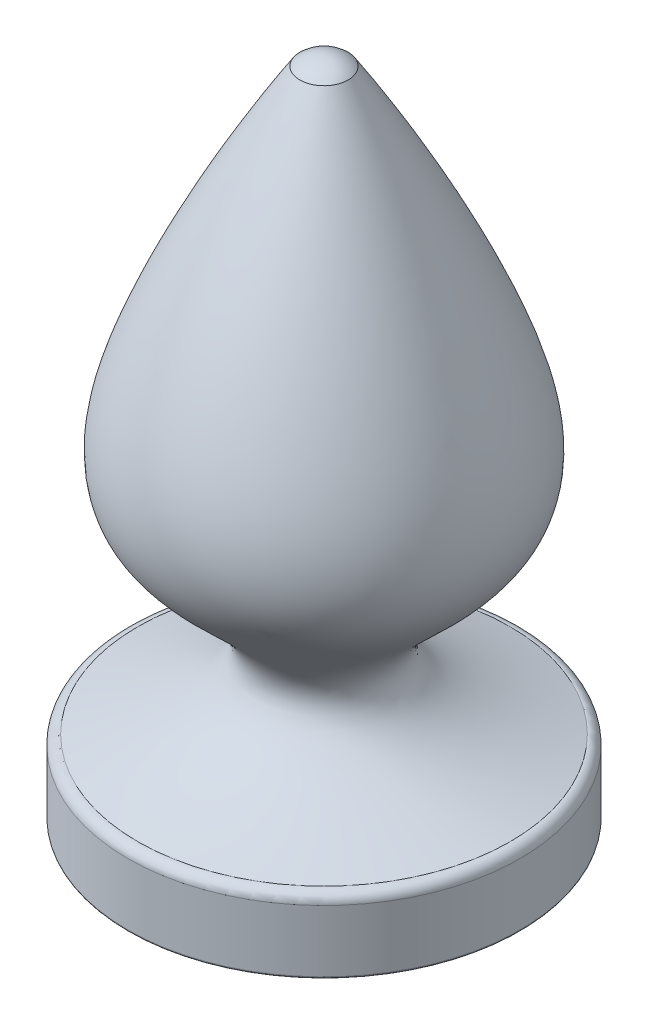
SolidWorks part; units mm, degrees
ref_plane "Front Plane" through (0, 0, 0) normal (0, 0, 1) x (1, 0, 0)
ref_plane "Top Plane" through (0, 0, 0) normal (0, 1, 0) x (1, 0, 0)
ref_plane "Right Plane" through (0, 0, 0) normal (1, 0, 0) x (0, 0, -1)
sketch "Sketch1" plane through (0, 0, 0) normal (0, 0, 1) x (1, 0, 0)
  line L0 (0, -40.5705) -> (0, 40.5705)
  line L2 (25.4, -32.3155) -> (25.4, -40.5705)
  line L3 (25.4, -40.5705) -> (0, -40.5705)
  line L6 (0, 40.5705) -> (0, 45.1545)
  arc A0 (3.1256, 43.9236) -> (0, 45.1545) centre (0, 40.5705) ccw
  arc A2 (24.13, -31.0455) -> (25.4, -32.3155) centre (24.13, -32.3155) cw
  spline S0 degree 3 poles (3.1256, 43.9236) (6.2293, 39.1286) (18.6626, 18.4795) (26.4058, -12.5101) (-5.6157, -21.4739) (24.13, -31.0455) knots 0 0 0 0 0.389546 0.60325 1 1 1 1
  point P4 (0, 0)
  dimension "D2" = 3.1256
  dimension "D3" = 1.27
  dimension "D1" = 4.5839
  dimension "D4" = 10.1612
  dimension "D5" = 19.05
  dimension "D6" = 20.4848
  dimension "D7" = 25.4
  dimension "D8" = 13.2755
  dimension "D9" = 40.5705
  dimension "D12" = 5.6177
  dimension "D13" = 17.0365
  dimension "D14" = 31.0455
revolve "Revolve1" add sketch "Sketch1" angle 360 about L0
fillet "Fillet1" radius 0.254 1 edges at (0, -40.5705, -25.4)
sketch "Sketch5" plane through (0, -40.5705, 0) normal (0, -1, 0) x (1, 0, 0)
  line L0 (15.0283, 12.2328) -> (3.4887, 12.2328) construction
  text T0 "@" font "Circular Std Bold" height 25.4
  point P4 (0, 0)
extrude "Cut-Extrude2" cut sketch "Sketch5" against normal blind 1.524
sketch "Sketch2" plane through (0, -40.5705, 0) normal (0, -1, 0) x (1, 0, 0)
  circle A0 centre (0, 0) radius 21.336 construction
  circle A1 centre (0, 0) radius 19.2722
  circle A2 centre (0, 0) radius 25.4 construction
  circle A3 centre (0, 0) radius 20.066
  text T0 "@secret_buttholes est. 2013 cambridge, ma 02138 #secret_butthole" font "Trebuchet MS" height 3.048
  dimension "D1" = 4.064
  dimension "D2" = 1.27
  dimension "D3" = 0.7937
extrude "Cut-Extrude1" cut sketch "Sketch2" against normal blind 1.524
sketch "Sketch6" plane through (0, -40.5705, 0) normal (0, -1, 0) x (1, 0, 0)
  circle A0 centre (0, 0) radius 21.971
  circle A1 centre (0, 0) radius 23.5585
  circle A2 centre (0, 0) radius 25.146 construction
  dimension "D1" = 1.5875
  dimension "D2" = 1.5875
extrude "Cut-Extrude3" [suppressed] cut sketch "Sketch6" against normal blind 0.762
